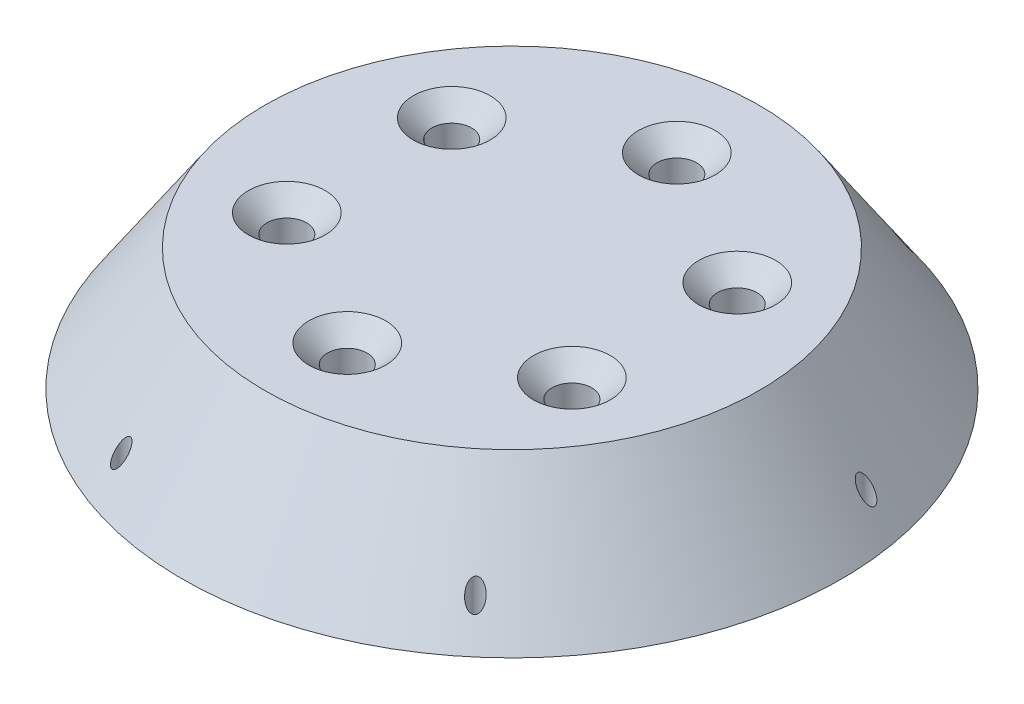
SolidWorks part; units mm, degrees
ref_plane "Front Plane" through (0, 0, 0) normal (0, 0, 1) x (1, 0, 0)
ref_plane "Top Plane" through (0, 0, 0) normal (0, 1, 0) x (1, 0, 0)
ref_plane "Right Plane" through (0, 0, 0) normal (1, 0, 0) x (0, 0, -1)
sketch "Sketch1" plane through (0, 0, 0) normal (0, 0, 1) x (1, 0, 0)
  line L0 (0, 0) -> (40.5, 0)
  line L1 (40.5, 0) -> (40.5, -20)
  line L2 (40.5, -20) -> (-13.5, -20)
  line L4 (0, 0) -> (-13.5, -20)
  line L5 (40.5, 11.5386) -> (40.5, -56.1152) construction
revolve "Revolve1" add sketch "Sketch1" angle 360 about L5
sketch "Sketch4" plane through (0, 0, 0) normal (0, 1, 0) x (1, 0, 0)
  line L0 (40.5, 0) -> (40.5, 53.3132) construction
  line L1 (40.4689, 0.018) -> (40.5, 27.018) construction
  line L2 (40.5, 0.018) -> (40.5, 27.018) construction
  circle A2 centre (40.5, 0) radius 27.018
  circle A4 centre (40.5, 27.018) radius 7.05
  circle A5 centre (63.8361, -13.5089) radius 7.05
  circle A6 centre (17.0707, -13.4551) radius 7.05
  circle A7 centre (63.8827, 13.518) radius 7.05
  circle A8 centre (63.8827, -13.482) radius 7.05
  circle A9 centre (40.5, -26.982) radius 7.05
  circle A10 centre (17.1173, -13.482) radius 7.05
  circle A11 centre (17.1173, 13.518) radius 7.05
  dimension "D1" = 3
  dimension "D2" = 27
  dimension "D4" = 27
  dimension "D3" = 6
hole_wizard "CSK for ST6.3 Cross recessed CTSK head tapping screws1" positions "Sketch7" profile "Sketch8" countersink size "ST6.3" standard "GB" end condition through all
sketch "Sketch7" plane through (0, 0, 0) normal (0, 1, 0) x (1, 0, 0)
  point P0 (17.0707, -13.4551)
  point P3 (63.8361, -13.5089)
  point P6 (40.5, 27.018)
sketch "Sketch8" plane through (17.0707, 0, 13.4551) normal (1, 0, 0) x (0, 0, 1)
  line L0 (0, 0) -> (0, 20)
  line L1 (0, 20) -> (3.25, 20)
  line L2 (3.25, 20) -> (3.25, 3.05)
  line L3 (3.25, 3.05) -> (6.3, 0)
  line L5 (6.3, 0) -> (0, 0)
  line L6 (-3.25, 3.05) -> (-6.3, 0) construction
  line L11 (0, -6.35) -> (0, 107.95) construction
  dimension "Thru Hole Dia." = 6.5
  dimension "Thru Hole Depth" = 20
  dimension "Near C'Sink Dia." = 12.6
  dimension "Near C'Sink Angle" = 90
sketch "Sketch9" plane through (0, -20, 0) normal (0, -1, 0) x (1, 0, 0)
  line L0 (40.5, 0) -> (72.7306, 38.2255) construction
  circle A0 centre (40.5, 0) radius 50
  circle A1 centre (72.7306, 38.2255) radius 1.25
  circle A2 centre (89.7196, -8.7997) radius 1.25
  circle A3 centre (57.489, -47.0253) radius 1.25
  circle A4 centre (8.2694, -38.2255) radius 1.25
  circle A5 centre (-8.7196, 8.7997) radius 1.25
  circle A6 centre (23.511, 47.0253) radius 1.25
  dimension "D1" = 6
hole_wizard "CSK for ST6.3 Cross recessed CTSK head tapping screws2" positions "Sketch10" profile "Sketch11" countersink size "ST6.3" standard "GB" end condition through all
sketch "Sketch10" plane through (0, 0, 0) normal (0, 1, 0) x (1, 0, 0)
  circle A0 centre (40.5, 0) radius 27.018 construction
  point P0 (17.1173, 13.518)
  point P3 (63.8827, 13.5359)
  point P7 (40.5, -26.982)
sketch "Sketch11" plane through (17.1173, 0, -13.518) normal (1, 0, 0) x (0, 0, 1)
  line L0 (0, 0) -> (0, 20)
  line L1 (0, 20) -> (3.25, 20)
  line L2 (3.25, 20) -> (3.25, 3.05)
  line L3 (3.25, 3.05) -> (6.3, 0)
  line L5 (6.3, 0) -> (0, 0)
  line L6 (-3.25, 3.05) -> (-6.3, 0) construction
  line L11 (0, -6.35) -> (0, 107.95) construction
  dimension "Thru Hole Dia." = 6.5
  dimension "Thru Hole Depth" = 20
  dimension "Near C'Sink Dia." = 12.6
  dimension "Near C'Sink Angle" = 90
extrude "Cut-Extrude1" cut sketch "Sketch9" against normal blind 50 contours A2
extrude "Cut-Extrude2" cut sketch "Sketch9<3>" against normal blind 50 contours A1
sketch "Sketch9<3>" plane through (0, -20, 0) normal (0, -1, 0) x (1, 0, 0) same geometry as "Sketch9"
extrude "Cut-Extrude3" cut sketch "Sketch9<4>" against normal blind 50 contours A6
sketch "Sketch9<4>" plane through (0, -20, 0) normal (0, -1, 0) x (1, 0, 0) same geometry as "Sketch9"
extrude "Cut-Extrude4" cut sketch "Sketch9<5>" against normal blind 50 contours A5
sketch "Sketch9<5>" plane through (0, -20, 0) normal (0, -1, 0) x (1, 0, 0) same geometry as "Sketch9"
extrude "Cut-Extrude5" cut sketch "Sketch9<7>" against normal blind 50 contours A4
sketch "Sketch9<7>" plane through (0, -20, 0) normal (0, -1, 0) x (1, 0, 0) same geometry as "Sketch9"
extrude "Cut-Extrude6" cut sketch "Sketch9<8>" against normal blind 50 contours A3
sketch "Sketch9<8>" plane through (0, -20, 0) normal (0, -1, 0) x (1, 0, 0) same geometry as "Sketch9"
